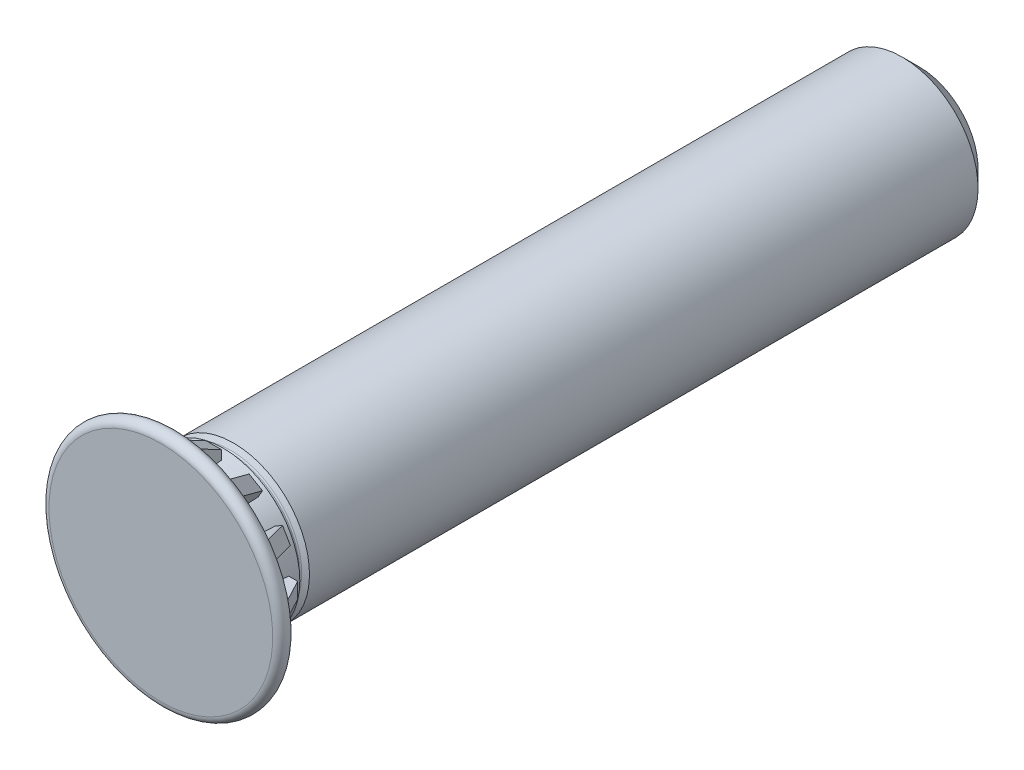
SolidWorks part; units mm, degrees
ref_plane "Front Plane" through (0, 0, 0) normal (0, 0, 1) x (1, 0, 0)
ref_plane "Top Plane" through (0, 0, 0) normal (0, 1, 0) x (1, 0, 0)
ref_plane "Right Plane" through (0, 0, 0) normal (1, 0, 0) x (0, 0, -1)
sketch "Sketch1" plane through (0, 0, 0) normal (1, 0, 0) x (0, 0, -1)
  line L0 (10, 0) -> (-10, 0) construction
  line L1 (10, 2) -> (10, -2) construction
  line L2 (-10, 3.15) -> (-10, -3.15) construction
  line L3 (10, -2) -> (-10, -2) construction
  line L4 (10, 2) -> (-10, 2) construction
  line L5 (9.9562, 2.0758) -> (10.3062, 1.4696) construction
  line L6 (10.3062, 1.4696) -> (10.6562, 2.0758) construction
  line L7 (10.6562, 2.0758) -> (9.9562, 2.0758) construction
  line L8 (10, 2) -> (10.6125, 2) construction
  line L9 (10.3062, 2.0758) -> (10.3062, 2) construction
  line L10 (10.3062, 2) -> (10.3062, 1.5453) construction
  line L11 (10.3062, 1.5453) -> (10.3062, 1.4696) construction
  line L12 (10.2625, 1.5453) -> (10.35, 1.5453)
  line L13 (9.9781, 2.0379) -> (10.6344, 2.0379)
  line L14 (10.35, 1.5453) -> (10.6344, 2.0379)
  line L15 (10.2625, 1.5453) -> (9.9781, 2.0379)
  point P8 (7.55, -2)
  point P10 (-7.6, 0)
  point P11 (-7.6, 2)
  point P24 (10.3062, 2.0379)
  point P25 (-7.6, -2)
  point P26 (-8.6, -2)
  point P28 (-8.6, 0)
  point P32 (10.3062, 1.5074)
  dimension "Thread Size" = 4
  dimension "Length" = 20
  dimension "Base Diameter" = 6.3
  dimension "Thread Pitch" = 0.7
  dimension "D3" = 0.0875
  dimension "For Minimum Material Thickness" = 1
  dimension "Unthreaded Length" = 2.4
  dimension "Thread Length" = 17.6
  dimension "D1" = 2.45
sketch "Sketch2" plane through (0, 0, 0) normal (0, 0, 1) x (1, 0, 0)
  circle A0 centre (0, 0) radius 2
sketch "Sketch7" plane through (0, 0, 0) normal (1, 0, 0) x (0, 0, -1)
  line L0 (10, 1.5453) -> (9.5453, 2)
  line L1 (10, 2) -> (10, -2) construction
  line L2 (10, 2) -> (-10, 2) construction
  line L3 (9.5453, 2) -> (-8.0816, 2)
  line L4 (-8.0816, 2) -> (-8.1691, 1.8484)
  line L5 (-8.1691, 1.8484) -> (-8.2566, 1.8484)
  line L6 (-8.2566, 1.8484) -> (-8.355, 2.0189)
  line L7 (-8.355, 2.0189) -> (-9.6, 2) construction
  line L9 (-9.6, 3.15) -> (-10, 3.15) construction
  line L11 (-10, 0) -> (10, 0)
  line L12 (10, 0) -> (10, 1.5453)
  line L13 (10.2625, 1.5453) -> (9.9781, 2.0379) construction
  line L14 (10.35, 1.5453) -> (10.6344, 2.0379) construction
  line L15 (10.2625, 1.5453) -> (10.35, 1.5453) construction
  line L16 (-10, 3.15) -> (-10, -3.15) construction
  line L17 (-9.6, 2) -> (-9.6, 2.95)
  line L18 (-10, 2.95) -> (-10, 0)
  line L19 (-8.355, 2.0189) -> (-9.6, 1.8484)
  line L20 (-9.6, 1.8484) -> (-9.6, 2)
  line L21 (9.5453, 2) -> (9.5453, 1.8484) construction
  line L22 (9.5453, 1.8484) -> (9.5453, 1.6969) construction
  line L23 (9.5453, 1.6969) -> (9.5453, 1.5453) construction
  line L24 (9.9781, 2.0379) -> (9.9781, 2) construction
  arc A0 (-9.6, 2.95) -> (-10, 2.95) centre (-9.8, 2.95) ccw
  point P10 (9.7727, 1.7727)
  point P32 (9.9781, 2.0189)
  dimension "D2" = 45
  dimension "D3" = 0.4
  dimension "D4" = 0.245
  dimension "D5" = 0.0875
revolve "Revolve3" add sketch "Sketch7" angle 360 about L0
fillet "Fillet2" radius 0.0437 2 edges at (0, 1.8484, 8.1691) (0, 1.8484, 8.2566)
sketch "Sketch16" plane through (0, 0, -10) normal (0, 0, -1) x (-1, 0, 0)
  circle A0 centre (0, 0) radius 1.5074
extrude "Cut-Extrude3" cut sketch "Sketch16" against normal blind 0.175 draft 30
sketch "Sketch13" plane through (0, 0, -9.825) normal (0, 0, -1) x (-1, 0, 0)
  circle A0 centre (0, 0) radius 0.5
  dimension "D1" = 1
extrude "Cut-Extrude1" cut sketch "Sketch13" against normal through all draft 45
sketch "Sketch9" plane through (0, 0, 0) normal (1, 0, 0) x (0, 0, -1)
  line L0 (-9.6, 2.5787) -> (-9.3, 2.5787)
  line L2 (-9.3, 2.5787) -> (-8.6, 2.2075)
  line L3 (-8.6, 2.2075) -> (-8.6, 0)
  line L4 (-8.6, 0) -> (-9.6, 0)
  line L5 (-9.6, -1.8484) -> (-9.6, 1.8484) construction
  line L6 (-9.6, 0) -> (-9.6, 2.5787)
  line L7 (-8.355, 2.0189) -> (-8.355, 2.396) construction
  line L8 (-8.355, 2.396) -> (-8.355, 2.773) construction
  line L9 (-8.6, 0) -> (0, 0) construction
  line L10 (-8.355, 2.773) -> (-8.355, 3.15) construction
  line L11 (-8.6, 2.2075) -> (-8.6, 2.95) construction
  line L12 (-9.6, 2) -> (-9.6, 2.95) construction
  point P13 (-9.45, 2.5787)
  point P18 (-8.355, 2.2075)
  point P28 (-8.6, 2.5787)
  dimension "D3" = 0.3
  dimension "D1" = 5.1575
extrude "Boss-Extrude1" add sketch "Sketch9" along normal mid plane 0.4095
pattern_circular "CirPattern3" count 12 over 360 about axis through (0, 0, -10) along (0, 0, 1) of "Boss-Extrude1"
sketch "Sketch14" plane through (0, 0, 9.6) normal (0, 0, -1) x (-1, 0, 0)
  circle A0 centre (0, 0) radius 2.3209
  dimension "D1" = 4.6417
extrude "Boss-Extrude3" add sketch "Sketch14" along normal up to vertex (0.15 mm away) up to point (0, 2.5787, 9.45)
ref_plane "Plane2" [suppressed] through (0, 0, -10) normal (0, 0, 1) x (1, 0, 0)
sketch "Sketch10" [suppressed] plane through (0, 0, -10) normal (0, 0, 1) x (1, 0, 0)
  circle A4 centre (0, 0) radius 2
curve "Helix/Spiral1" [suppressed] pitch 0.7 height 18.3 turns 26.1429
ref_plane "Plane1" [suppressed] through (0, 0, 7.6) normal (0, 0, 1) x (1, 0, 0)
split "Split1" [suppressed] bodies to split 131
sketch "Sketch11" [suppressed] plane through (0, 0, 0) normal (1, 0, 0) x (0, 0, -1)
  line L0 (10.2625, 1.5453) -> (10.35, 1.5453) construction
  line L1 (10.2625, 1.5453) -> (9.9781, 2.0379) construction
  line L2 (9.9781, 2.0379) -> (10.6344, 2.0379) construction
  line L3 (10.35, 1.5453) -> (10.6344, 2.0379) construction
  line L4 (10.2625, 1.5453) -> (10.35, 1.5453)
  line L5 (10.2625, 1.5453) -> (9.9781, 2.0379)
  line L6 (9.9781, 2.0379) -> (10.6344, 2.0379)
  line L7 (10.35, 1.5453) -> (10.6344, 2.0379)
sweep "Cut-Sweep1" [suppressed] cut profiles "Sketch11" path "Helix/Spiral1"
sketch "Sketch12" [suppressed] plane through (0, 0, 7.6) normal (0, 0, 1) x (1, 0, 0)
  circle A1 centre (0, 0) radius 2
  circle A3 centre (0, 0) radius 2
  dimension "D1" = 0
extrude "Boss-Extrude2" [suppressed] add sketch "Sketch12" against normal through all draft 55
equation "\"D3@Sketch1\" = \"Thread Pitch@Sketch1\" / 8"
equation "\"D3@Sketch7\" = \"Thread Pitch@Sketch1\" / 1.75"
equation "\"D4@Sketch7\"=\"Thread Pitch@Sketch1\" * 0.35"
equation "\"D1@Boss-Extrude1\"=\"Base Diameter@Sketch1\"*0.065"
equation "\"D4@Helix/Spiral1\" = \"Thread Pitch@Sketch1\""
equation "\"D3@Helix/Spiral1\" = \"Thread Length@Sketch1\" + \"Thread Pitch@Sketch1\""
equation "\"D1@Sketch1\" = \"Thread Pitch@Sketch1\" * 3.5"
equation "\"D1@Fillet2\"=\"D5@Sketch7\"*0.5"
equation "\"D1@Sketch13\"=\"For Hole Diameter@Sketch2\"*0.25"
equation "\"D1@Sketch14\"=\"D1@Sketch9\"*0.9"
equation "\"D3@Sketch9\"=\"D3@Sketch7\"*0.75"
equation "\"D1@Cut-Extrude3\"=\"Thread Pitch@Sketch1\"*0.25"
